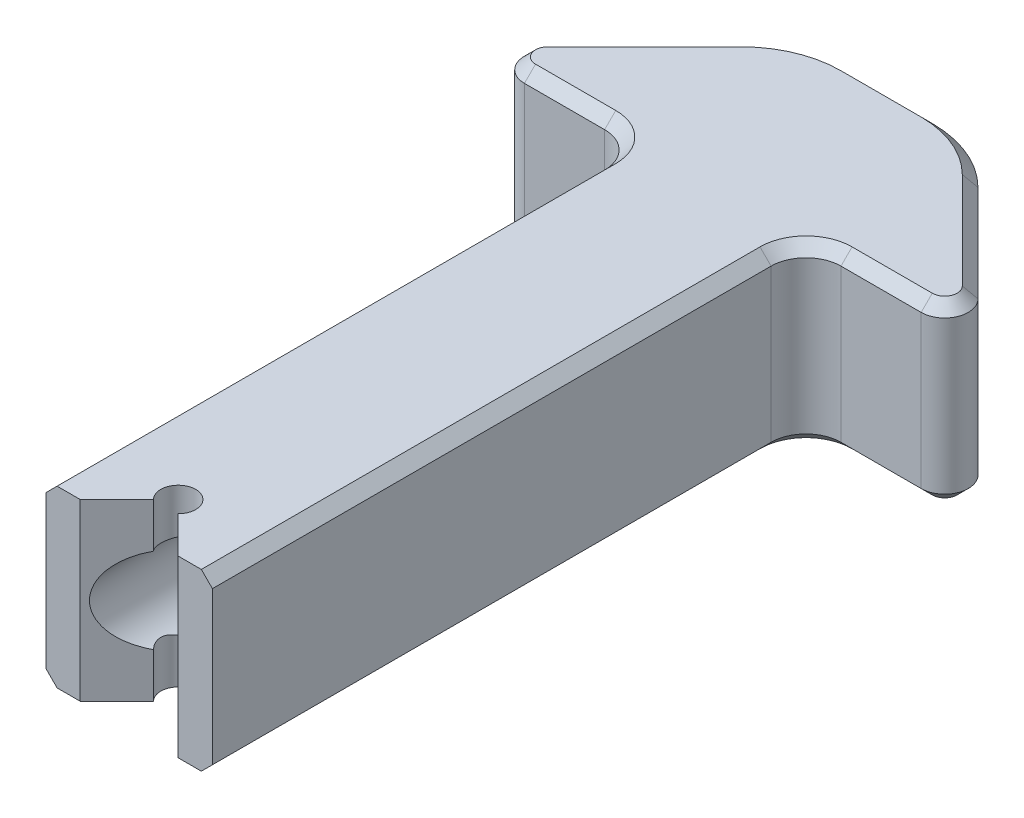
SolidWorks part; units mm, degrees
material "AISI 304"
ref_plane "Front Plane" through (0, 0, 0) normal (0, 0, 1) x (1, 0, 0)
ref_plane "Top Plane" through (0, 0, 0) normal (0, 1, 0) x (1, 0, 0)
ref_plane "Right Plane" through (0, 0, 0) normal (1, 0, 0) x (0, 0, -1)
sketch "Sketch1" plane through (0, 0, 0) normal (0, 1, 0) x (1, 0, 0)
  line L3 (0, 0) -> (4.6625, 0)
  line L4 (0, 0) -> (-1.6875, 0)
  line L5 (-1.6875, 0) -> (-1.6875, 1.524)
  line L6 (-1.6875, 1.524) -> (4.5355, 7.747)
  line L7 (4.5355, 7.747) -> (8.4725, 7.747)
  line L8 (8.4725, 7.747) -> (8.4725, -27.178)
  line L9 (4.6625, 0) -> (4.6625, -27.178)
  line L18 (4.6625, -27.178) -> (8.4725, -27.178)
  circle A1 centre (-0.6099, 1.0776) radius 1.0776
  point P4 (-1.9611, 0.889)
  point P8 (-1.9641, 0.889)
  point P11 (5.2975, 7.874)
  dimension "D1" = 3.81
  dimension "D2" = 7.747
  dimension "D3" = 10.16
  dimension "D4" = 135
  dimension "D6" = 3.937
  dimension "D7" = 34.925
extrude "Boss-Extrude1" add sketch "Sketch1" along normal blind 8.001 contours A1 L4 L3 L9 L18 L8 L7 L6 | A1 region at (5.9269, 0, 7.6498) region at (-0.6099, 0, -1.0776)
ref_plane "Plane1" through (8.4725, 0, 0) normal (1, 0, 0) x (0, 0, -1)
mirror "Mirror1" about plane through (8.4725, 0, 0) normal (1, 0, 0) of "Boss-Extrude1"
sketch "Sketch4" plane through (0, 0, -7.747) normal (0, 0, -1) x (-1, 0, 0)
  line L2 (-8.4725, 0) -> (-8.4725, 8.001) construction
  line L5 (-4.5355, 0) -> (-12.4095, 0) construction
  line L6 (-4.5355, 8.001) -> (-12.4095, 8.001) construction
  circle A0 centre (-8.4725, 4.0005) radius 2.032
  dimension "D1" = 4.064
extrude "Cut-Extrude1" cut sketch "Sketch4" against normal blind 50.8
sketch "Sketch5" plane through (0, 0, -7.747) normal (0, 0, -1) x (-1, 0, 0)
  circle A0 centre (-8.4725, 4.0005) radius 3.048
  circle A1 centre (-8.4725, 4.0005) radius 2.032 construction
  dimension "D1" = 6.096
extrude "Cut-Extrude2" cut sketch "Sketch5" against normal blind 4.572
sketch "Sketch7" plane through (0, 8.001, 0) normal (0, 1, 0) x (1, 0, 0)
  line L0 (4.6625, -27.178) -> (12.2825, -27.178) construction
  line L1 (6.2274, -27.178) -> (10.7176, -27.178)
  line L2 (6.2274, -27.178) -> (8.4725, -24.9329)
  line L3 (8.4725, -24.9329) -> (10.7176, -27.178)
  circle A0 centre (8.4725, -24.9329) radius 0.8001
  point P7 (8.4725, -27.178)
  line M8 (4.6625, -27.178) -> (12.2825, -27.178)
  dimension "D2" = 1.6002
  dimension "D1" = 3.175
extrude "Cut-Extrude4" cut sketch "Sketch7" against normal through all contours L3 A0 L2 | L2 A0 L3 | A0 L2 L3 M8 region at (8.4725, 8.001, 26.5423) region at (8.4725, 8.001, 24.7729) region at (8.4725, 8.001, 25.4132)
fillet "Fillet2" radius 5.08 2 edges at (4.5355, 4.0005, -7.747) (12.4095, 4.0005, -7.747)
fillet "Fillet3" radius 1.6002 2 edges at (12.2825, 4.0005, 0) (4.6625, 4.0005, 0)
chamfer "Chamfer1" distance 0.508 angle 45 26 edges at (12.2825, 8.001, 14.3891) (12.7512, 8.001, 0.4687) (15.7188, 8.001, 0) (18.5505, 8.001, -0.6652) (16.1071, 8.001, -4.0494) (12.2493, 8.001, -7.3603) (8.4725, 8.001, -7.747) (4.6957, 8.001, -7.3603) (0.8379, 8.001, -4.0494) (-1.6055, 8.001, -0.6652) (1.2262, 8.001, 0) (4.1938, 8.001, 0.4687) (4.6625, 8.001, 14.3891) (4.6625, 0, 14.3891) (4.1938, 0, 0.4687) (1.2262, 0, 0) (-1.6055, 0, -0.6652) (0.8379, 0, -4.0494) (4.6957, 0, -7.3603) (8.4725, 0, -7.747) (12.2493, 0, -7.3603) (16.1071, 0, -4.0494) (18.5505, 0, -0.6652) (15.7188, 0, 0) (12.7512, 0, 0.4687) (12.2825, 0, 14.3891)
sketch "Sketch8" plane through (0, 0, 0) normal (0, -1, 0) x (1, 0, 0)
  line L11 (17.5549, -0.508) -> (13.8827, -0.508) construction
  line L12 (13.5382, -5.8999) -> (17.9577, -1.4804) construction
  line L13 (6.6397, -7.239) -> (10.3053, -7.239) construction
  line L14 (-1.0126, -1.4804) -> (3.4068, -5.8999) construction
  line L15 (3.0623, -0.508) -> (-0.6099, -0.508) construction
  line L16 (17.5549, -0.508) -> (13.8827, -0.508)
  line L17 (13.5382, -5.8999) -> (17.9577, -1.4804)
  line L18 (6.6397, -7.239) -> (10.3053, -7.239)
  line L19 (-1.0126, -1.4804) -> (3.4068, -5.8999)
  line L20 (3.0623, -0.508) -> (-0.6099, -0.508)
  line L21 (3.0623, -0.508) -> (13.8827, -0.508)
  arc A8 (17.9577, -1.4804) -> (17.5549, -0.508) centre (17.5549, -1.0776) ccw construction
  arc A9 (10.3053, -7.239) -> (13.5382, -5.8999) centre (10.3053, -2.667) ccw construction
  arc A10 (3.4068, -5.8999) -> (6.6397, -7.239) centre (6.6397, -2.667) ccw construction
  arc A11 (-0.6099, -0.508) -> (-1.0126, -1.4804) centre (-0.6099, -1.0776) ccw construction
  arc A12 (17.9577, -1.4804) -> (17.5549, -0.508) centre (17.5549, -1.0776) ccw
  arc A13 (10.3053, -7.239) -> (13.5382, -5.8999) centre (10.3053, -2.667) ccw
  arc A14 (3.4068, -5.8999) -> (6.6397, -7.239) centre (6.6397, -2.667) ccw
  arc A15 (-0.6099, -0.508) -> (-1.0126, -1.4804) centre (-0.6099, -1.0776) ccw
split line "Split Line1"
